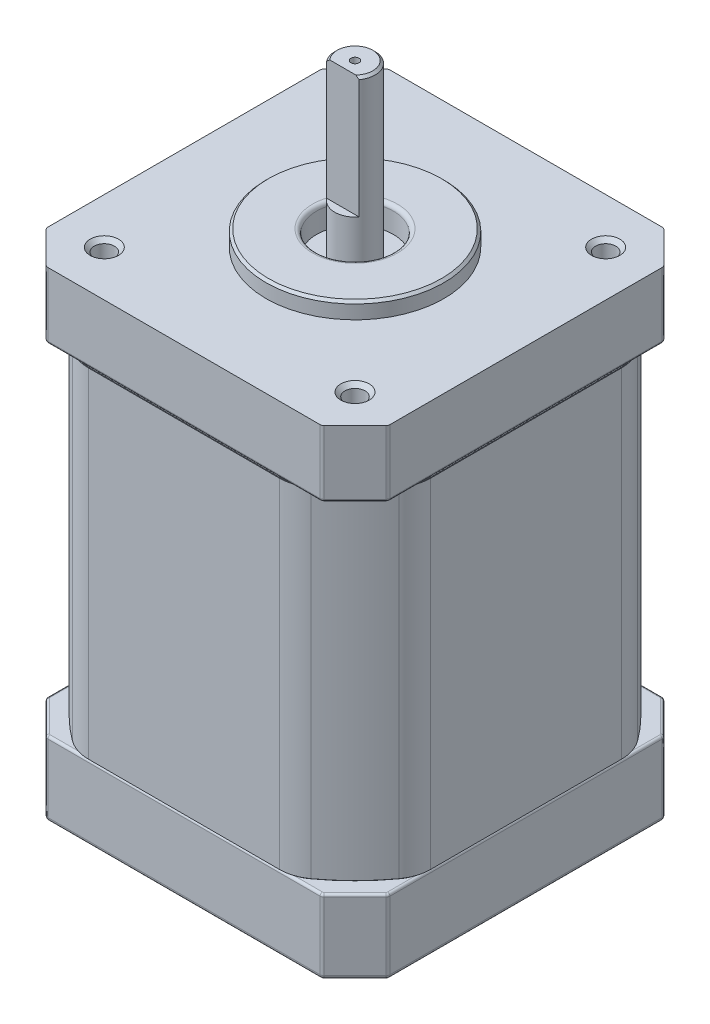
SolidWorks part; units mm, degrees
ref_plane "Спереди" through (0, 0, 0) normal (0, 0, 1) x (1, 0, 0)
ref_plane "Сверху" through (0, 0, 0) normal (0, 1, 0) x (1, 0, 0)
ref_plane "Справа" through (0, 0, 0) normal (1, 0, 0) x (0, 0, -1)
sketch "Эскиз1" plane through (0, 0, 0) normal (0, 1, 0) x (1, 0, 0)
  line L0 (-21.15, 17.0338) -> (-17.0338, 21.15)
  line L1 (-21.15, 21.15) -> (21.15, 21.15)
  line L2 (-21.15, 21.15) -> (-21.15, -21.15)
  line L3 (-21.15, -21.15) -> (21.15, -21.15)
  line L4 (21.15, 21.15) -> (21.15, -21.15)
  line L5 (-21.15, 21.15) -> (21.15, -21.15) construction
  line L6 (-21.15, -21.15) -> (21.15, 21.15) construction
  line L7 (-17.0338, 21.15) -> (17.0338, 21.15)
  line L8 (17.0338, 21.15) -> (21.15, 17.0338)
  line L9 (21.15, 17.0338) -> (21.15, -17.0338)
  line L10 (21.15, -17.0338) -> (17.0338, -21.15)
  line L11 (17.0338, -21.15) -> (-17.0338, -21.15)
  line L12 (-17.0338, -21.15) -> (-21.15, -17.0338)
  point P0 (0, 0)
  dimension "D1" = 42.3
  dimension "D2" = 54
extrude "Бобышка-Вытянуть1" add sketch "Эскиз1" along normal blind 9.2 contours L12 L3 L10 L4 L8 L1 L0 L2 region at (0, 0, 0)
extrude "Бобышка-Вытянуть2" add sketch "Эскиз1<3>" against normal blind 8.2 from offset 59.4 separate body contours L12 L3 L10 L4 L8 L1 L0 L2 region at (0, 0, 0)
sketch "Эскиз1<3>" plane through (0, 0, 0) normal (0, 1, 0) x (1, 0, 0) same geometry as "Эскиз1"
sketch "Эскиз2" plane through (0, 9.2, 0) normal (0, 1, 0) x (1, 0, 0)
  line L16 (-21.15, -17.0338) -> (-17.0338, -21.15)
  line L17 (-17.0338, -21.15) -> (17.0338, -21.15)
  line L18 (17.0338, -21.15) -> (21.15, -17.0338)
  line L19 (21.15, -17.0338) -> (21.15, 17.0338)
  line L20 (21.15, 17.0338) -> (17.0338, 21.15)
  line L21 (17.0338, 21.15) -> (-17.0338, 21.15)
  line L22 (-17.0338, 21.15) -> (-21.15, 17.0338)
  line L23 (-21.15, 17.0338) -> (-21.15, -17.0338)
  line L25 (-11.7974, -21.15) -> (11.7974, -21.15)
  line L27 (21.15, -11.7974) -> (21.15, 11.7974)
  line L29 (11.7974, 21.15) -> (-11.7974, 21.15)
  line L31 (-21.15, 11.7974) -> (-21.15, -11.7974)
  arc A0 (-20.1875, -14.7467) -> (-14.7467, -20.1875) centre (0, 0) ccw
  arc A1 (-14.7467, 20.1875) -> (-20.1875, 14.7467) centre (0, 0) ccw
  arc A2 (20.1875, 14.7467) -> (14.7467, 20.1875) centre (0, 0) ccw
  arc A3 (14.7467, -20.1875) -> (20.1875, -14.7467) centre (0, 0) ccw
  arc A4 (14.7467, 20.1875) -> (11.7974, 21.15) centre (11.7974, 16.15) ccw
  arc A5 (21.15, 11.7974) -> (20.1875, 14.7467) centre (16.15, 11.7974) ccw
  arc A6 (20.1875, -14.7467) -> (21.15, -11.7974) centre (16.15, -11.7974) ccw
  arc A7 (11.7974, -21.15) -> (14.7467, -20.1875) centre (11.7974, -16.15) ccw
  arc A8 (-14.7467, -20.1875) -> (-11.7974, -21.15) centre (-11.7974, -16.15) ccw
  arc A9 (-20.1875, -14.7467) -> (-21.15, -11.7974) centre (-16.15, -11.7974) cw
  arc A10 (-20.1875, 14.7467) -> (-21.15, 11.7974) centre (-16.15, 11.7974) ccw
  arc A11 (-11.7974, 21.15) -> (-14.7467, 20.1875) centre (-11.7974, 16.15) ccw
  point P22 (21.15, 13.3296)
  point P27 (13.3296, -21.15)
  point P36 (-13.3296, 21.15)
  dimension "D1" = 50
  dimension "D3" = 5
  dimension "D2" = 0
extrude "Бобышка-Вытянуть3" add sketch "Эскиз2" along normal blind 42 separate body
fillet "Скругление1" radius 0.5 16 edges at (0, 0, 21.15) (19.0919, 0, 19.0919) (21.15, 0, 0) (19.0919, 0, -19.0919) (0, 0, -21.15) (-19.0919, 0, -19.0919) (-21.15, 0, 0) (-19.0919, 0, 19.0919) (21.15, 4.6, 17.0338) (17.0338, 4.6, 21.15) (-17.0338, 4.6, 21.15) (-21.15, 4.6, 17.0338) (-21.15, 4.6, -17.0338) (-17.0338, 4.6, -21.15) (17.0338, 4.6, -21.15) (21.15, 4.6, -17.0338)
fillet "Скругление2" radius 0.5 8 edges at (21.15, 55.3, 17.0338) (17.0338, 55.3, 21.15) (-17.0338, 55.3, 21.15) (-21.15, 55.3, 17.0338) (-21.15, 55.3, -17.0338) (-17.0338, 55.3, -21.15) (17.0338, 55.3, -21.15) (21.15, 55.3, -17.0338)
sketch "Эскиз6" plane through (0, 59.4, 0) normal (0, 1, 0) x (1, 0, 0)
  circle A0 centre (0, 0) radius 11
  circle A1 centre (0, 0) radius 4.75
  dimension "D1" = 22
  dimension "D2" = 9.5
extrude "Бобышка-Вытянуть4" add sketch "Эскиз6" along normal blind 2
sketch "Эскиз7" plane through (0, 59.4, 0) normal (0, 1, 0) x (1, 0, 0)
  circle A2 centre (0, 0) radius 4.75
  circle A3 centre (0, 0) radius 4.75
  dimension "D1" = 0
extrude "Вырез-Вытянуть4" cut sketch "Эскиз7" against normal blind 1
chamfer "Фаска2" distance 0.3 angle 45 1 edges at (0, 61.4, 11)
fillet "Скругление3" radius 0.5 1 edges at (0, 61.4, 4.75)
sketch "Эскиз8" plane through (0, 58.4, 0) normal (0, 1, 0) x (1, 0, 0)
  circle A0 centre (0, 0) radius 2.5
  dimension "D1" = 5
extrude "Бобышка-Вытянуть5" add sketch "Эскиз8" along normal blind 21
chamfer "Фаска4" distance 0.3 angle 45 1 edges at (0, 79.4, 2.5)
sketch "Эскиз9" plane through (0, 79.4, 0) normal (0, 1, 0) x (1, 0, 0)
  circle A0 centre (0, 0) radius 0.5
  dimension "D1" = 1
extrude "Вырез-Вытянуть5" cut sketch "Эскиз9" against normal blind 1
chamfer "Фаска34" distance 0.05 angle 45 32 edges at (-17.6777, 51.2, -17.6777) (-20.9033, 51.2, -13.3486) (-13.3486, 51.2, -20.9033) (-21.15, 51.2, 0) (0, 51.2, -21.15) (-20.9033, 51.2, 13.3486) (13.3486, 51.2, -20.9033) (-17.6777, 51.2, 17.6777) (17.6777, 51.2, -17.6777) (-13.3486, 51.2, 20.9033) (20.9033, 51.2, -13.3486) (0, 51.2, 21.15) (21.15, 51.2, 0) (13.3486, 51.2, 20.9033) (20.9033, 51.2, 13.3486) (17.6777, 51.2, 17.6777) (-17.6777, 9.2, -17.6777) (-20.9033, 9.2, -13.3486) (-13.3486, 9.2, -20.9033) (-21.15, 9.2, 0) (0, 9.2, -21.15) (-20.9033, 9.2, 13.3486) (13.3486, 9.2, -20.9033) (-17.6777, 9.2, 17.6777) (17.6777, 9.2, -17.6777) (-13.3486, 9.2, 20.9033) (20.9033, 9.2, -13.3486) (0, 9.2, 21.15) (21.15, 9.2, 0) (13.3486, 9.2, 20.9033) (20.9033, 9.2, 13.3486) (17.6777, 9.2, 17.6777)
sketch "Эскиз16" plane through (0, 59.4, 0) normal (0, 1, 0) x (1, 0, 0)
  line L1 (-15.5, 15.5) -> (15.5, 15.5) construction
  line L2 (-15.5, 15.5) -> (-15.5, -15.5) construction
  line L3 (-15.5, -15.5) -> (15.5, -15.5) construction
  line L4 (15.5, 15.5) -> (15.5, -15.5) construction
  line L5 (-15.5, 15.5) -> (15.5, -15.5) construction
  line L6 (-15.5, -15.5) -> (15.5, 15.5) construction
  circle A0 centre (-15.5, 15.5) radius 1.25
  circle A1 centre (15.5, 15.5) radius 1.25
  circle A2 centre (15.5, -15.5) radius 1.25
  circle A3 centre (-15.5, -15.5) radius 1.25
  point P0 (0, 0)
  dimension "D1" = 2.5
  dimension "D2" = 31
extrude "Вырез-Вытянуть9" cut sketch "Эскиз16" against normal blind 7
chamfer "Фаска35" distance 0.5 angle 45 4 edges at (-15.5, 59.4, 16.75) (15.5, 59.4, 16.75) (15.5, 59.4, -14.25) (-15.5, 59.4, -14.25)
fillet "Скругление4" radius 0.3 16 edges at (0, 9.2, 21.15) (-17.018, 9.2, 21.1119) (-19.0919, 9.2, 19.0919) (-21.1119, 9.2, 17.018) (-21.15, 9.2, 0) (-21.1119, 9.2, -17.018) (-19.0919, 9.2, -19.0919) (-17.018, 9.2, -21.1119) (0, 9.2, -21.15) (17.018, 9.2, -21.1119) (19.0919, 9.2, -19.0919) (21.1119, 9.2, -17.018) (21.15, 9.2, 0) (21.1119, 9.2, 17.018) (17.018, 9.2, 21.1119) (19.0919, 9.2, 19.0919)
fillet "Скругление5" radius 0.3 16 edges at (21.1119, 51.2, 17.018) (21.15, 51.2, 0) (21.1119, 51.2, -17.018) (19.0919, 51.2, -19.0919) (17.018, 51.2, -21.1119) (0, 51.2, -21.15) (-17.018, 51.2, -21.1119) (-19.0919, 51.2, -19.0919) (-21.1119, 51.2, -17.018) (-21.15, 51.2, 0) (-21.1119, 51.2, 17.018) (-19.0919, 51.2, 19.0919) (-17.018, 51.2, 21.1119) (0, 51.2, 21.15) (17.018, 51.2, 21.1119) (19.0919, 51.2, 19.0919)
sketch "Эскиз17" plane through (0, 79.4, 0) normal (0, 1, 0) x (1, 0, 0)
  line L1 (-2.5, -3) -> (2.5, -3)
  line L2 (-2.5, -3) -> (-2.5, -1.5)
  line L3 (-2.5, -1.5) -> (2.5, -1.5)
  line L4 (2.5, -3) -> (2.5, -1.5)
  circle A0 centre (0, 0) radius 2.5 construction
  circle A1 centre (0, 0) radius 2.5 construction
  dimension "D1" = 1.5
  dimension "D2" = 1.5
extrude "Вырез-Вытянуть10" cut sketch "Эскиз17" against normal blind 15
